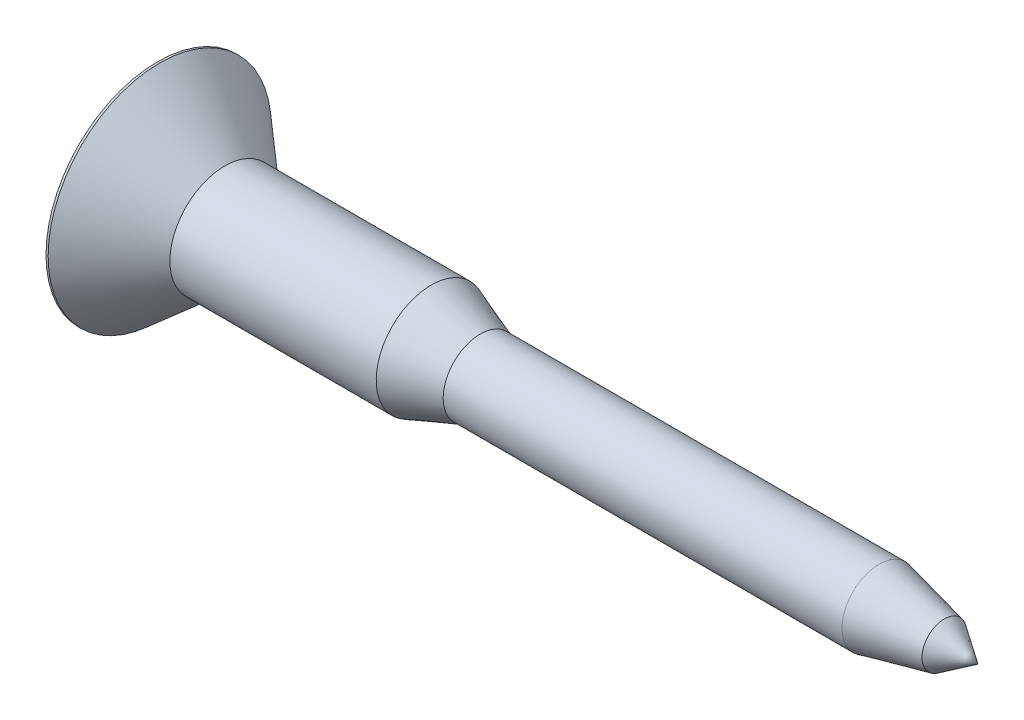
SolidWorks part; units mm, degrees
ref_plane "Front Plane" through (0, 0, 0) normal (0, 0, 1) x (1, 0, 0)
ref_plane "Top Plane" through (0, 0, 0) normal (0, 1, 0) x (1, 0, 0)
ref_plane "Right Plane" through (0, 0, 0) normal (1, 0, 0) x (0, 0, -1)
sketch "Sketch1" plane through (0, 0, 0) normal (0, 0, 1) x (1, 0, 0)
  line L0 (-25.4, 0) -> (25.4, 0) construction
  line L1 (-25.4, 0) -> (-25.4, 6.9088)
  line L2 (-25.4, 6.9088) -> (-25.2667, 6.9088)
  line L3 (-25.2667, 6.9088) -> (-21.2344, 3.4036)
  line L4 (-21.2344, 3.4036) -> (25.4, 3.4036)
  line L5 (25.4, 0) -> (25.4, 3.4036)
  line L6 (25.4, 0.1702) -> (19.2735, 2.2974) construction
  line L7 (-8.4582, 0) -> (-8.4582, 3.4036) construction
  line L9 (25.4, 2.2974) -> (25.4, 3.4036) construction
  line L10 (25.4, 2.8505) -> (-8.4582, 2.8505) construction
  line L11 (-25.4, 4.8966) -> (-25.4, -4.8966) construction
  line L12 (-16.7894, 1.7907) -> (-16.7894, -1.7907) construction
  line L13 (25.2236, 2.545) -> (26.6347, 4.9891) construction
  line L14 (-12.6238, 1.9812) -> (-12.6238, -1.9812) construction
  line L15 (26.6347, 4.9891) -> (28.0458, 2.545) construction
  line L16 (28.0458, 2.545) -> (25.2236, 2.545) construction
  line L17 (26.6347, 4.9891) -> (26.6347, 4.6836) construction
  line L18 (26.4583, 4.6836) -> (26.8111, 4.6836) construction
  line L19 (26.6347, 2.8505) -> (26.6347, 2.545) construction
  line L20 (25.3118, 2.6978) -> (27.9576, 2.6978) construction
  line L21 (25.4, 2.8505) -> (27.8694, 2.8505) construction
  line L22 (-21.2344, -3.4036) -> (-25.2667, -6.9088) construction
  line L23 (-21.2344, 3.4036) -> (-21.2344, -3.4036) construction
  line L24 (-25.2667, -6.9088) -> (-25.2667, 6.9088) construction
  line L25 (-25.2667, -6.9088) -> (-25.4, -6.9088)
  point P2 (-8.4582, 0)
  point P8 (25.4, 2.2974)
  point P9 (25.4, -3.4036)
  point P14 (15.0402, -3.4036)
  point P21 (-12.6238, 0)
  point P22 (-16.7894, 0)
  point P36 (26.6347, 4.6836)
  point P42 (26.6347, 2.6978)
  point P43 (-22.2758, 0)
  point P44 (-21.2344, 0)
  dimension "Length" = 50.8
  dimension "Head Diameter" = 13.8176
  dimension "Minimum Thread Length" = 33.8582
  dimension "Screw Size Decimal Equivalent" = 6.8072
  dimension "D2" = 6.1265
  dimension "D4" = 19.148
  dimension "D3" = 27.7317
  dimension "D5" = 0.3404
  dimension "D6" = 3.4036
  dimension "Head Height" = 4.1656
  dimension "D7" = 4.5949
  dimension "D8" = 4.2333
  dimension "D9" = 4.1656
  dimension "D10" = 4.1656
  dimension "Softwood Drill Bit Size Decimal Equivalent" = 3.5814
  dimension "Hardwood Drill Bit Size Decimal Equivalent" = 3.9624
  dimension "Pitch" = 2.8222
  dimension "D11" = 0.3528
  dimension "D12" = 3.1242
  dimension "Countersink Angle" = 82
ref_plane "Plane1" through (19.2735, 0, 0) normal (1, 0, 0) x (0, 0, -1)
sketch "Sketch13" plane through (0, 0, 0) normal (0, 0, 1) x (1, 0, 0)
  line L0 (-25.4, 0) -> (-25.4, 6.9088) construction
  line L2 (-21.2344, 3.4036) -> (25.4, 3.4036) construction
  line L3 (-25.4, 0) -> (-25.4, 6.9088)
  line L4 (-25.2667, 6.9088) -> (-21.2344, 3.4036)
  line L5 (-21.2344, 3.4036) -> (-8.4582, 3.4036)
  line L7 (-25.4, 6.9088) -> (-25.2667, 6.9088)
  line L8 (-8.4582, 3.4036) -> (-5.419, 2.2974)
  line L9 (-5.419, 2.2974) -> (19.2735, 2.2974)
  line L10 (19.2735, 2.2974) -> (23.3121, 1.3825)
  line L11 (23.3121, 1.3825) -> (25.4, 0)
  line L12 (-25.4, 0) -> (25.4, 0) construction
  line L13 (-25.4, 0) -> (25.4, 0)
  dimension "D1" = 20
  dimension "D2" = 33.509
  dimension "D3" = 12.765
revolve "Revolve2" add sketch "Sketch13" angle 360 about L12
sketch "Sketch2" [suppressed] plane through (19.2735, 0, 0) normal (1, 0, 0) x (0, 0, -1)
  circle A0 centre (0, 0) radius 3.4036
sketch "Sketch4" [suppressed] plane through (19.2735, 0, 0) normal (1, 0, 0) x (0, 0, -1)
  circle A1 centre (0, 0) radius 3.4036
  circle A2 centre (0, 0) radius 3.4036
  dimension "D1" = 0
sketch "Sketch9" plane through (0, 0, 0) normal (1, 0, 0) x (0, 0, -1)
  line L0 (0.6218, -1.6484) -> (0.6218, -3.5235)
  line L1 (0.6218, 3.5235) -> (-0.6218, 3.5235)
  line L2 (0.6218, 3.5235) -> (0.6218, 1.6484)
  line L3 (0.6218, -3.5235) -> (-0.6218, -3.5235)
  line L4 (-0.6218, 3.5235) -> (-0.6218, 1.6484)
  line L5 (3.5235, 0.6218) -> (1.6484, 0.6218)
  line L6 (3.5235, 0.6218) -> (3.5235, -0.6218)
  line L7 (3.5235, -0.6218) -> (1.6484, -0.6218)
  line L8 (-3.5235, 0.6218) -> (-3.5235, -0.6218)
  line L9 (-1.6484, -0.6218) -> (-3.5235, -0.6218)
  line L10 (-1.6484, 0.6218) -> (-3.5235, 0.6218)
  line L11 (-0.6218, -1.6484) -> (-0.6218, -3.5235)
  line L12 (0, 0) -> (0, 3.5235) construction
  line L13 (0.6218, 0.6218) -> (1.2457, 1.2457) construction
  line L14 (1.6484, 0.6218) -> (0.9338, 0.9338)
  line L15 (0.9338, 0.9338) -> (0.6218, 1.6484)
  line L16 (-1.6484, 0.6218) -> (-0.9338, 0.9338)
  line L17 (-0.9338, 0.9338) -> (-0.6218, 1.6484)
  line L18 (0, 0) -> (3.5235, 0) construction
  line L19 (-1.6484, -0.6218) -> (-0.9338, -0.9338)
  line L20 (-0.9338, -0.9338) -> (-0.6218, -1.6484)
  line L21 (0.9338, -0.9338) -> (0.6218, -1.6484)
  line L22 (1.6484, -0.6218) -> (0.9338, -0.9338)
  circle A0 centre (0, 0) radius 3.5235 construction
  circle A1 centre (0, 0) radius 1.7617 construction
  point P0 (0, 0)
  dimension "D1" = 3.5235
  dimension "D2" = 7.047
  dimension "D3" = 1.2436
extrude "Boss-Extrude1" add sketch "Sketch9" along normal up to vertex (-22.2758 mm away) from vertex separate body up to point (-22.2758, 0, 0) starting at point (-25.4, 0, 0)
sketch "Sketch10" plane through (0, 0, 0) normal (0, 0, 1) x (1, 0, 0)
  line L0 (-24.9657, 3.5235) -> (-22.2758, 1.9073)
  line L3 (-22.2758, 3.5235) -> (-25.4, 3.5235) construction
  line L4 (-22.2758, 3.5235) -> (-22.2758, 1.9073)
  line L6 (-24.9657, 3.5235) -> (-22.2758, 3.5235)
  line L7 (-22.2758, 3.5235) -> (-22.2758, 1.6484) construction
  line L8 (-25.2667, 6.9088) -> (-21.2344, 3.4036) construction
  dimension "D1" = 0.4343
  dimension "D2" = 10
extrude "Cut-Extrude2" cut sketch "Sketch10" against normal through all both and the other way through all
draft "Draft2" type of draft neutral plane draft angle 3 faces to draft 8 face at (-23.8379, 0.7778, 1.2911) face at (-23.8379, 1.2911, 0.7778) face at (-23.8379, 1.2911, -0.7778) face at (-23.8379, 0.7778, -1.2911) face at (-23.8379, -0.7778, -1.2911) face at (-23.8379, -1.2911, -0.7778) face at (-23.8379, -0.7778, 1.2911) face at (-23.8379, -1.2911, 0.7778) neutral plane through (-25.4, 0, 0) neutral plane normal (-1, 0, 0) reverse direction yes parameters "D1"=3
pattern_circular "CirPattern3" count 4 over 360 about axis through (23.3121, 0, 0) along (1, 0, 0) of "Cut-Extrude2"
combine bodies "Combine2" operation type subtract main body 126 bodies to subtract 128
curve "Helix/Spiral1" [suppressed] pitch 2.8222 height 30.5539 turns 10.8262 parameters "Pitch"=2.8222
sketch "Sketch3" [suppressed] plane through (0, 0, 0) normal (0, 0, 1) x (1, 0, 0)
  line L0 (19.4499, 3.4036) -> (20.0886, 2.2974) construction
  line L1 (19.4499, 3.4036) -> (19.0971, 3.4036)
  line L2 (19.0971, 3.4036) -> (18.4585, 2.2974) construction
  line L3 (18.4585, 2.2974) -> (20.0886, 2.2974) construction
  line L4 (19.4499, 3.4036) -> (19.2735, 3.4036) construction
  line L5 (19.2735, 3.4036) -> (19.2735, 2.2974) construction
  line L6 (-21.2344, 3.4036) -> (25.4, 3.4036) construction
  line L7 (19.4499, 3.4036) -> (20.3319, 1.876)
  line L8 (20.3319, 1.876) -> (18.2152, 1.876)
  line L9 (18.2152, 1.876) -> (19.0971, 3.4036)
  dimension "D2" = 0.3528
  dimension "D3" = 2.1167
  dimension "D1" = 60
sweep "Sweep1" [suppressed] add profiles "Sketch3" path "Helix/Spiral1"
curve "Helix/Spiral2" [suppressed]
sketch "Sketch5" [suppressed] plane through (0, 0, 0) normal (0, 0, 1) x (1, 0, 0)
  line L4 (19.0971, 3.4036) -> (18.2152, 1.876)
  line L5 (19.0971, 3.4036) -> (18.2152, 1.876)
  line L6 (18.2152, 1.876) -> (20.3319, 1.876)
  line L7 (19.4499, 3.4036) -> (19.0971, 3.4036)
  line L8 (18.2152, 1.876) -> (20.3319, 1.876)
  line L9 (20.3319, 1.876) -> (19.4499, 3.4036)
  line L10 (20.3319, 1.876) -> (19.4499, 3.4036)
  line L11 (19.4499, 3.4036) -> (19.0971, 3.4036)
  dimension "D1" = 0
sweep "Sweep2" [suppressed] add profiles "Sketch5" path "Helix/Spiral2"
sketch "Sketch14" [suppressed] plane through (0, 0, 0) normal (0, 0, 1) x (1, 0, 0)
  line L0 (-8.4582, 0) -> (-8.4582, 2.8505)
  line L1 (-8.4582, 2.8505) -> (-7.5002, 3.4036)
  line L2 (-7.5002, 3.4036) -> (-25.4, 3.4036)
  line L3 (-25.4, 3.4036) -> (-25.4, 0)
  line L4 (-25.4, 0) -> (-8.4582, 0) construction
  line L5 (-25.4, 0) -> (25.4, 0) construction
  line L6 (-21.2344, 3.4036) -> (25.4, 3.4036) construction
  line L7 (-8.4582, 0) -> (-8.4582, 3.4036) construction
  line L8 (-8.4582, 0) -> (-25.4, 0)
  line L9 (28.4577, 3.4036) -> (28.4577, 0)
  line L10 (28.4577, 0) -> (24.3417, 0)
  line L11 (24.3417, 0) -> (24.3417, 0.7007)
  line L12 (24.3417, 0.7007) -> (22.3423, 3.4036)
  line L13 (22.3423, 3.4036) -> (28.4577, 3.4036)
  line L14 (25.4, 0) -> (25.4, 3.4036) construction
  line L16 (23.3121, 1.3825) -> (25.4, 0) construction
  dimension "D1" = 30
  dimension "D2" = 1.0583
  dimension "D3" = 20
revolve "Cut-Revolve2" [suppressed] cut sketch "Sketch14" angle 360 about L4
combine bodies "Combine1" [suppressed] operation type add bodies to combine 127 131
equation "\"D2@Sketch1\" = \"Screw Size Decimal Equivalent@Sketch1\" * .90"
equation "\"D6@Helix/Spiral2\"=\"D4@Sketch1\"*1"
equation "\"D5@Sketch1\" = \"Screw Size Decimal Equivalent@Sketch1\" * .05"
equation "\"D3@Helix/Spiral2\"=\"D2@Sketch1\""
equation "\"D4@Helix/Spiral2\"=\"Pitch@Sketch1\""
equation "\"D3@Helix/Spiral1\" = \"D3@Sketch1\" + \"Pitch@Sketch1\""
equation "\"D6@Sketch1\" = \"Screw Size Decimal Equivalent@Sketch1\" / 2"
equation "\"D2@Sketch3\" = \"Pitch@Sketch1\" * .125"
equation "\"D1@Sketch9\"=(\"Head Diameter@Sketch1\"*.51)/2"
equation "\"D7@Sketch1\" = \"Screw Size Decimal Equivalent@Sketch1\" * .6750"
equation "\"D2@Sketch13\"=\"D4@Sketch1\"*1.750"
equation "\"D3@Sketch13\"= \"D4@Sketch1\" / 1.50"
equation "\"D2@Sketch14\"=\"D3@Sketch3\"/2"
equation "\"D8@Sketch1\" = \"Pitch@Sketch1\" * 1.50"
equation "\"D10@Sketch1\"=\"Head Height@Sketch1\""
equation "\"D9@Sketch1\"=\"Head Height@Sketch1\""
equation "\"D11@Sketch1\"=\"Pitch@Sketch1\"/8"
equation "\"D2@Sketch9\"=\"Head Diameter@Sketch1\"*.51"
equation "\"D3@Sketch9\"=\"Head Diameter@Sketch1\"*.09"
equation "\"D12@Sketch1\"=\"Head Height@Sketch1\"*.75"
equation "\"Pitch@Helix/Spiral1\"=\"Pitch@Sketch1\""
equation "\"D3@Sketch3\"=\"Pitch@Sketch1\"*.75"
